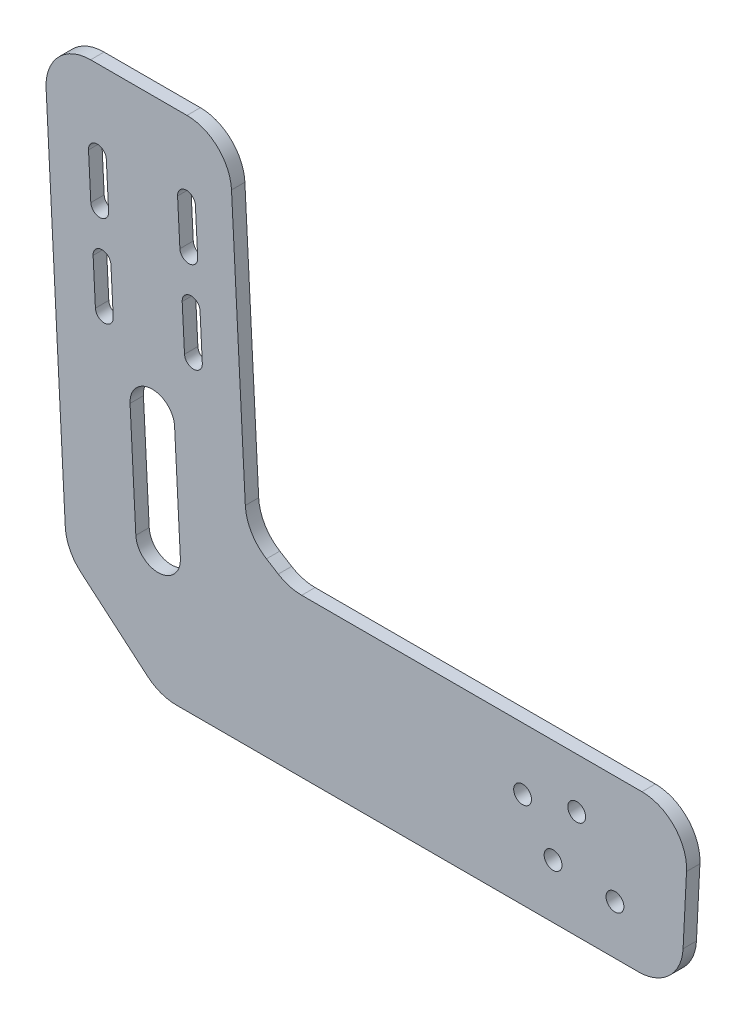
SolidWorks part; units mm, degrees
ref_plane "Front Plane" through (0, 0, 0) normal (0, 0, 1) x (1, 0, 0)
ref_plane "Top Plane" through (0, 0, 0) normal (0, 1, 0) x (1, 0, 0)
ref_plane "Right Plane" through (0, 0, 0) normal (1, 0, 0) x (0, 0, -1)
sketch "Sketch1" plane through (0, 0, 0) normal (0, 0, 1) x (1, 0, 0)
  line L0 (96, 288) -> (480, 288) construction
  line L5 (139.8875, 204.0569) -> (141.2478, 208.2423)
  line L6 (141.2478, 208.2423) -> (144.8357, 210.0701)
  line L7 (144.8357, 210.0701) -> (160.5008, 210.0701)
  line L8 (160.5008, 210.0701) -> (167.6223, 208.2423)
  line L9 (167.6223, 208.2423) -> (172.5227, 205.8317)
  line L10 (172.5227, 205.8317) -> (175.6197, 203.6755)
  line L11 (175.6197, 203.6755) -> (178.9468, 200.2338)
  line L12 (178.9468, 200.2338) -> (179.0371, 200.0565)
  line L13 (179.0371, 200.0565) -> (183.516, 193.5019)
  line L14 (183.516, 193.5019) -> (185.3016, 187.4874)
  line L15 (185.3016, 187.4874) -> (185.5391, 184.5636)
  line L16 (185.5391, 184.5636) -> (184.9544, 182.3551)
  line L17 (184.9544, 182.3551) -> (184.1138, 181.11)
  line L18 (184.1138, 181.11) -> (182.6519, 180.178)
  line L19 (182.6519, 180.178) -> (181.2323, 180.178)
  line L20 (181.2323, 180.178) -> (171.2716, 180.178)
  line L21 (171.2716, 180.178) -> (153.6307, 182.3551)
  line L22 (153.6307, 182.3551) -> (151.9661, 182.7893)
  line L23 (151.9661, 182.7893) -> (149.3848, 183.3631)
  line L24 (149.3848, 183.3631) -> (148.2087, 184.3681)
  line L25 (148.2087, 184.3681) -> (147.1895, 185.6438)
  line L26 (147.1895, 185.6438) -> (145.0293, 190.8839)
  line L27 (145.0293, 190.8839) -> (141.6449, 197.2747)
  line L28 (141.6449, 197.2747) -> (139.8875, 204.0569)
extrude "Boss-Extrude1" add sketch "Sketch1" along normal blind 4
scale "Scale4" scale about centroid uniform scaling yes scale factor 0.75919
fillet "Fillet6" radius 3 15 edges at (170.0892, 203.1921, 2) (179.7908, 189.2653, 2) (175.0349, 198.8077, 2) (179.5272, 185.3689, 2) (178.4353, 193.8315, 2) (178.8891, 184.4237, 2) (169.1394, 183.7161, 2) (154.4829, 185.6986, 2) (155.7466, 185.3689, 2) (150.8565, 187.8657, 2) (151.6303, 186.8972, 2) (152.5232, 186.1343, 2) (177.7792, 183.7161, 2) (146.6471, 196.6958, 2) (149.2165, 191.8439, 2)
fillet "Fillet7" radius 3 4 edges at (145.3129, 201.8447, 2) (146.3456, 205.0223, 2) (160.9623, 206.4099, 2) (179.9712, 187.0457, 2)
sketch "Sketch2" plane through (0, 0, 3.5184) normal (0, 0, 1) x (1, 0, 0)
  line L16 (188.4341, 188.0922) -> (189.2069, 203.4681)
  line L17 (179.2195, 213.9701) -> (102.9192, 213.9701)
  line L18 (97.6721, 215.4573) -> (95.0194, 217.0924)
  line L19 (90.2799, 225.0878) -> (87.1857, 284.8068)
  line L23 (45.6123, 283.7719) -> (49.9132, 200.7646)
  line L24 (53.4221, 193.6637) -> (68.3445, 180.9758)
  line L25 (74.8221, 178.5942) -> (178.4467, 178.5942)
  line L26 (91.5968, 290.2016) -> (475.5968, 290.2016) construction
  line L27 (265.5233, 365.0561) -> (649.5233, 365.0561) construction
  line L28 (-12.3254, 339.1419) -> (371.6746, 339.1419) construction
  line L29 (57.1165, 276.6623) -> (57.6339, 266.6757) construction
  line L30 (59.1138, 276.7658) -> (59.6312, 266.7792)
  line L31 (55.1191, 276.5588) -> (55.6366, 266.5722)
  line L32 (77.0897, 277.6972) -> (77.6071, 267.7106) construction
  line L33 (79.087, 277.8007) -> (79.6044, 267.8141)
  line L34 (75.0924, 277.5937) -> (75.6098, 267.6071)
  line L35 (57.3752, 271.669) -> (77.3484, 272.7039) construction
  line L36 (57.1165, 276.6623) -> (77.0897, 277.6972) construction
  line L37 (42.8166, 260.9013) -> (76.0779, 262.6246) construction
  line L38 (58.6688, 246.7025) -> (58.1513, 256.6891) construction
  line L39 (60.6661, 246.806) -> (60.1487, 256.7926)
  line L40 (56.6715, 246.599) -> (56.154, 256.5856)
  line L41 (78.642, 247.7374) -> (78.1245, 257.724) construction
  line L42 (80.6393, 247.8409) -> (80.1219, 257.8275)
  line L43 (76.6447, 247.6339) -> (76.1272, 257.6205)
  line L46 (69.4315, 232.24) -> (70.7251, 207.2735) construction
  line L47 (74.4248, 232.4987) -> (75.7184, 207.5322)
  line L48 (64.4382, 231.9813) -> (65.7318, 207.0148)
  line L49 (55.5989, 294.2893) -> (77.1991, 294.2893)
  arc A0 (68.3445, 180.9758) -> (74.8221, 178.5942) centre (74.8221, 188.5942) ccw
  arc A1 (49.9132, 200.7646) -> (53.4221, 193.6637) centre (59.8998, 201.2821) ccw
  arc A3 (95.0194, 217.0924) -> (90.2799, 225.0878) centre (100.2665, 225.6052) cw
  arc A4 (102.9192, 213.9701) -> (97.6721, 215.4573) centre (102.9192, 223.9701) cw
  arc A5 (189.2069, 203.4681) -> (179.2195, 213.9701) centre (179.2195, 203.9701) ccw
  arc A6 (188.4341, 188.0922) -> (178.4467, 178.5942) centre (178.4467, 188.5942) cw
  circle A8 centre (173.1565, 189.5937) radius 2
  circle A9 centre (164.5809, 202.7514) radius 2
  circle A10 centre (159.2817, 190.7377) radius 2
  circle A11 centre (152.4442, 200.0749) radius 2
  arc A13 (59.1138, 276.7658) -> (55.1191, 276.5588) centre (57.1165, 276.6623) ccw
  arc A14 (55.6366, 266.5722) -> (59.6312, 266.7792) centre (57.6339, 266.6757) ccw
  arc A15 (79.087, 277.8007) -> (75.0924, 277.5937) centre (77.0897, 277.6972) ccw
  arc A16 (75.6098, 267.6071) -> (79.6044, 267.8141) centre (77.6071, 267.7106) ccw
  arc A17 (60.6661, 246.806) -> (56.6715, 246.599) centre (58.6688, 246.7025) cw
  arc A18 (56.154, 256.5856) -> (60.1487, 256.7926) centre (58.1513, 256.6891) cw
  arc A19 (80.6393, 247.8409) -> (76.6447, 247.6339) centre (78.642, 247.7374) cw
  arc A20 (76.1272, 257.6205) -> (80.1219, 257.8275) centre (78.1245, 257.724) cw
  arc A23 (74.4248, 232.4987) -> (64.4382, 231.9813) centre (69.4315, 232.24) ccw
  arc A24 (65.7318, 207.0148) -> (75.7184, 207.5322) centre (70.7251, 207.2735) ccw
  arc A25 (87.1857, 284.8068) -> (77.1991, 294.2893) centre (77.1991, 284.2893) ccw
  arc A26 (45.6123, 283.7719) -> (55.5989, 294.2893) centre (55.5989, 284.2893) cw
  point P26 (57.3752, 271.669)
  point P33 (77.3484, 272.7039)
  point P64 (58.4101, 251.6958)
  point P71 (78.3833, 252.7307)
  point P82 (70.0783, 219.7568)
  point P87 (67.3618, 272.1864)
  dimension "D1" = 10
  dimension "D2" = 4
  dimension "D3" = 4
  dimension "D4" = 4
  dimension "D5" = 5
  dimension "D6" = 2
  dimension "D7" = 2
  dimension "D12" = 10
  dimension "D8" = 20
  dimension "D9" = 30
  dimension "D10" = 10
  dimension "D11" = 10
  dimension "D13" = 25
extrude "Boss-Extrude2" add sketch "Sketch2" along normal blind 3
sketch "Sketch3" plane through (0, 0, 3.5184) normal (0, 0, 1) x (1, 0, 0)
  circle A0 centre (173.1565, 189.5937) radius 2 construction
  circle A1 centre (164.5809, 202.7514) radius 2
  circle A2 centre (164.5809, 202.7514) radius 2
  circle A3 centre (173.1565, 189.5937) radius 2
  dimension "D1" = 0
extrude "Cut-Extrude1" cut sketch "Sketch3" against normal blind 10
sketch "Sketch4" plane through (0, 0, 6.5184) normal (0, 0, 1) x (1, 0, 0)
  line L0 (152.5396, 156.754) -> (536.5396, 156.754) construction
